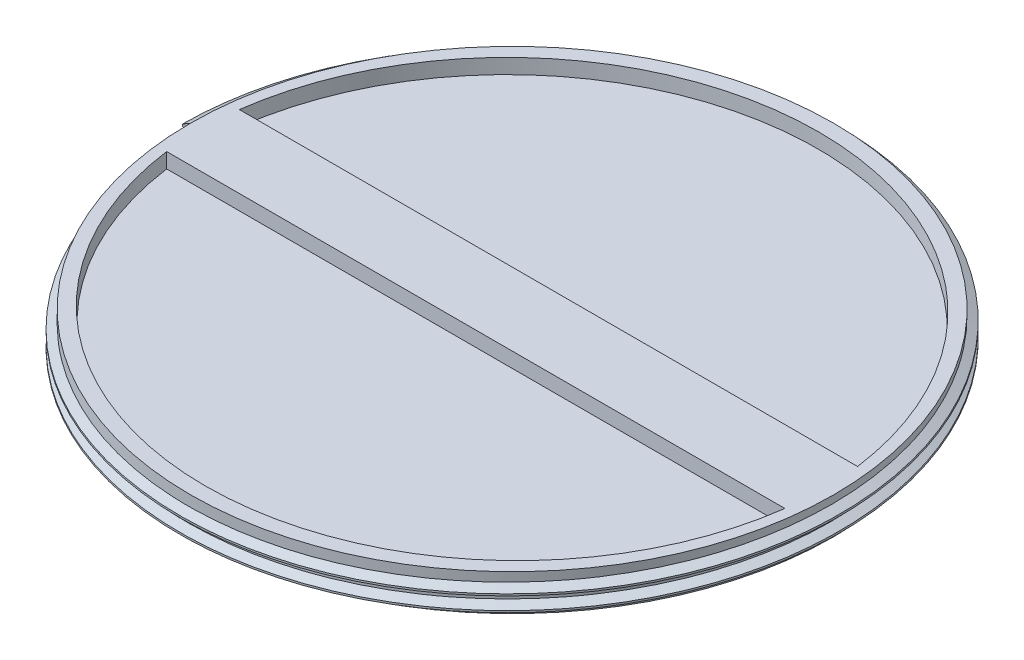
SolidWorks part; units mm, degrees
ref_plane "Front Plane" through (0, 0, 0) normal (0, 0, 1) x (1, 0, 0)
ref_plane "Top Plane" through (0, 0, 0) normal (0, 1, 0) x (1, 0, 0)
ref_plane "Right Plane" through (0, 0, 0) normal (1, 0, 0) x (0, 0, -1)
sketch "Sketch1" plane through (0, 0, 0) normal (0, 1, 0) x (1, 0, 0)
  circle A0 centre (0, 0) radius 44.25
  dimension "D1" = 88.5
extrude "Boss-Extrude2" add sketch "Sketch1" along normal blind 5
ref_plane "Plane1" through (0, 0, 45) normal (0, 0, 1) x (1, 0, 0)
thread "Thread1" pitch 2 method extrude profile "Thread Profile1" start angle 0, offset 0, length 4, pitch 2, diameter 88.5
ref_plane "Plane2" through (-44.25, 5, 0) normal (0, 0, 1) x (-1, 0, 0)
sketch "Thread Profile1" plane through (-44.25, 5, 0) normal (0, 0, 1) x (-1, 0, 0)
  line L0 (0, 0) -> (0, 2) construction
  line L1 (0, 0) -> (1.0825, 0.625)
  line L2 (1.0825, 0.625) -> (1.0825, 0.875)
  line L3 (1.0825, 0.875) -> (0, 1.5)
  line L4 (1.0825, 0.75) -> (0, 0.75) construction
  line L11 (0, 0) -> (0, 1.5)
  point P2 (0, 0)
  dimension "Pitch" = 2
  dimension "Profile_Angle" = 60
  dimension "Profile_Land" = 0.25
  dimension "Profile_Height" = 1.0825
ref_plane "Plane3" through (0, 0, 10) normal (0, 0, 1) x (1, 0, 0)
sketch "Sketch5" plane through (0, 5, 0) normal (0, 1, 0) x (1, 0, 0)
  line L1 (42.516, 5) -> (-42.516, 5) construction
  line L2 (42.516, 5) -> (42.516, -5) construction
  line L3 (42.516, -5) -> (-42.516, -5)
  line L4 (-42.516, 5) -> (-42.516, -5) construction
  line L5 (42.516, 5) -> (-42.516, -5) construction
  line L6 (42.516, -5) -> (-42.516, 5) construction
  arc A0 (-42.516, -5) -> (42.516, -5) centre (0, 0.7189) ccw
  point P0 (0, 0)
  dimension "D1" = 10
extrude "Cut-Extrude2" cut sketch "Sketch5" against normal blind 2 draft 2
mirror "Mirror1" about plane through (0, 0, 0) normal (0, 0, 1) of "Cut-Extrude2"
